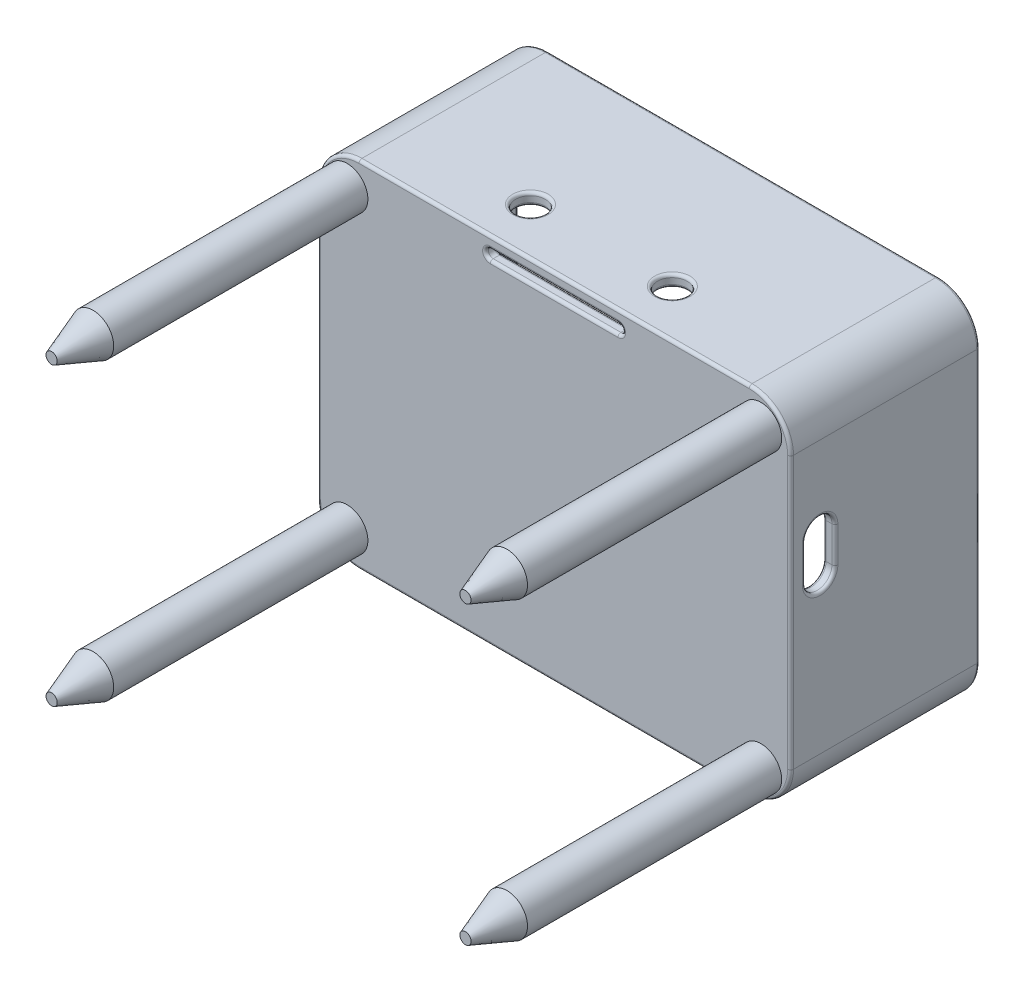
SolidWorks part; units mm, degrees
ref_plane "Plan de face" through (0, 0, 0) normal (0, 0, 1) x (1, 0, 0)
ref_plane "Plan de dessus" through (0, 0, 0) normal (0, 1, 0) x (1, 0, 0)
ref_plane "Plan de droite" through (0, 0, 0) normal (1, 0, 0) x (0, 0, -1)
sketch "Esquisse2" plane through (0, 0, 0) normal (0, 0, 1) x (1, 0, 0)
  line L5 (-33, -30) -> (33, -30)
  line L6 (-40, -23) -> (-40, 23)
  line L7 (-33, 30) -> (33, 30)
  line L8 (40, -23) -> (40, 23)
  line L9 (-40, -30) -> (40, 30) construction
  line L10 (-40, 30) -> (40, -30) construction
  arc A0 (33, 30) -> (40, 23) centre (33, 23) cw
  arc A1 (40, -23) -> (33, -30) centre (33, -23) cw
  arc A2 (-40, -23) -> (-33, -30) centre (-33, -23) ccw
  arc A3 (-40, 23) -> (-33, 30) centre (-33, 23) cw
  point P0 (0, 0)
  dimension "D3" = 7
  dimension "D1" = 60
  dimension "D2" = 80
extrude "Boss.-Extru.1" add sketch "Esquisse2" along normal blind 2
sketch "Esquisse3" plane through (0, 0, 2) normal (0, 0, 1) x (1, 0, 0)
  line L0 (33, 30) -> (-33, 30) construction
  line L1 (-40, 23) -> (-40, -23) construction
  line L2 (-33, -30) -> (33, -30) construction
  line L3 (40, -23) -> (40, 23) construction
  circle A0 centre (-35, 25) radius 3.5
  circle A1 centre (35, 25) radius 3.5
  circle A2 centre (35, -25) radius 3.5
  circle A3 centre (-35, -25) radius 3.5
  dimension "D1" = 7
  dimension "D2" = 5
  dimension "D3" = 5
  dimension "D4" = 5
  dimension "D5" = 5
extrude "Boss.-Extru.2" add sketch "Esquisse3" along normal blind 50
chamfer "Chanfrein1" distance 7 angle 20 4 edges at (38.5, 25, 52) (-31.5, 25, 52) (-31.5, -25, 52) (38.5, -25, 52) first distance on face at (38.5, 25, 52) first distance on face at (-31.5, 25, 52) first distance on face at (-31.5, -25, 52) first distance on face at (38.5, -25, 52)
sketch "Esquisse4" plane through (0, 0, 0) normal (0, 0, -1) x (-1, 0, 0)
  line L12 (-33, 30) -> (33, 30) construction
  line L13 (40, 23) -> (40, -23) construction
  line L14 (33, -30) -> (-33, -30) construction
  line L15 (-33, 30) -> (33, 30)
  line L16 (40, 23) -> (40, -23)
  line L17 (33, -30) -> (-33, -30)
  line L18 (-40, -23) -> (-40, 23) construction
  line L19 (-40, -23) -> (-40, 23)
  line L20 (-33, 28) -> (33, 28)
  line L21 (38, 23) -> (38, -23)
  line L22 (33, -28) -> (-33, -28)
  line L23 (-38, -23) -> (-38, 23)
  arc A0 (40, 23) -> (33, 30) centre (33, 23) ccw construction
  arc A1 (33, -30) -> (40, -23) centre (33, -23) ccw construction
  arc A2 (40, 23) -> (33, 30) centre (33, 23) ccw
  arc A3 (33, -30) -> (40, -23) centre (33, -23) ccw
  arc A4 (-33, 30) -> (-40, 23) centre (-33, 23) ccw construction
  arc A5 (-33, 30) -> (-40, 23) centre (-33, 23) ccw
  arc A6 (-40, -23) -> (-33, -30) centre (-33, -23) ccw construction
  arc A7 (-40, -23) -> (-33, -30) centre (-33, -23) ccw
  arc A8 (38, 23) -> (33, 28) centre (33, 23) ccw
  arc A9 (33, -28) -> (38, -23) centre (33, -23) ccw
  arc A10 (-38, -23) -> (-33, -28) centre (-33, -23) ccw
  arc A11 (-33, 28) -> (-38, 23) centre (-33, 23) ccw
  dimension "D1" = 2
extrude "Boss.-Extru.3" add sketch "Esquisse4" along normal blind 30
sketch "Esquisse5" plane through (40, 0, 0) normal (1, 0, 0) x (0, 0, -1)
  line L0 (3, 9.2) -> (3, 3.2) construction
  line L1 (5.5, 9.2) -> (5.5, 3.2)
  line L2 (0.5, 9.2) -> (0.5, 3.2)
  arc A0 (5.5, 9.2) -> (0.5, 9.2) centre (3, 9.2) ccw
  arc A1 (0.5, 3.2) -> (5.5, 3.2) centre (3, 3.2) ccw
  point P2 (3, 6.2)
  point P7 (3, 7.4852)
  point P8 (3, 11.7)
  point P10 (3, 0.7)
  dimension "D1" = 11
  dimension "D2" = 0.5
  dimension "D3" = 5
  dimension "D4" = 6.2
extrude "Enlèv. mat.-Extru.1" cut sketch "Esquisse5" against normal up to surface (2 mm away) contours L2 A1 L1 A0 up to face at (38, 0, -15)
sketch "Esquisse6" plane through (0, 0, 0) normal (0, 0, -1) x (-1, 0, 0)
  line L0 (-10.8, 27.2) -> (10.8, 27.2) construction
  line L1 (-10.8, 28) -> (10.8, 28)
  line L2 (-10.8, 26.4) -> (10.8, 26.4)
  line L5 (33, 28) -> (-33, 28) construction
  arc A0 (-10.8, 28) -> (-10.8, 26.4) centre (-10.8, 27.2) ccw
  arc A1 (10.8, 26.4) -> (10.8, 28) centre (10.8, 27.2) ccw
  point P0 (18.5903, 18.6488)
  point P3 (0, 27.2)
  point P10 (-11.6, 27.2)
  point P11 (11.6, 27.2)
  dimension "D1" = 23.2
  dimension "D2" = 1.6
extrude "Enlèv. mat.-Extru.2" cut sketch "Esquisse6" against normal up to surface (2 mm away) up to face at (-38.5, -25, 2)
sketch "Esquisse9" plane through (-12, 28, 0) normal (0, -1, 0) x (1, 0, 0)
  line L9 (2.5, -6) -> (21.5, -6) construction
  circle A0 centre (0, -6) radius 2.5
  circle A1 centre (24, -6) radius 2.5
  point P6 (0, 0)
  point P7 (0, 0)
  point P8 (12, -6)
  point P11 (-10.9255, -6)
  dimension "D1" = 5
  dimension "D2" = 6
  dimension "D3" = 19
extrude "Enlèv. mat.-Extru.4" cut sketch "Esquisse9" against normal up to next
sketch "Esquisse10" plane through (-38, 0, 0) normal (1, 0, 0) x (0, 0, -1)
  line L1 (20, 7.5) -> (25, 7.5)
  line L2 (20, 7.5) -> (20, -7.5)
  line L3 (20, -7.5) -> (25, -7.5)
  line L4 (25, 7.5) -> (25, -7.5)
  line L5 (14, -5) -> (14, 5) construction
  circle A0 centre (14, 5) radius 1.5
  circle A1 centre (14, -5) radius 1.5
  point P4 (20, 0)
  point P12 (14, 0)
  point P13 (14, 3.5)
  point P14 (14, -3.5)
  dimension "D4" = 3
  dimension "D1" = 5
  dimension "D2" = 15
  dimension "D3" = 14
  dimension "D5" = 7
  dimension "D6" = 6
extrude "Enlèv. mat.-Extru.5" cut sketch "Esquisse10" against normal through all
sketch "Esquisse11" plane through (0, 0, 0) normal (0, 0, -1) x (-1, 0, 0)
  line L0 (-38, 23) -> (-38, -23) construction
  line L1 (-38, 17.1) -> (-33.5, 17.1)
  line L2 (-38, 17.1) -> (-38, 15.1)
  line L3 (-38, 15.1) -> (-33.5, 15.1)
  line L4 (-33, 16.6) -> (-33, 15.6)
  line L6 (-38, -15.9) -> (-33.5, -15.9)
  line L7 (-38, -15.9) -> (-38, -13.9)
  line L8 (-38, -13.9) -> (-33.5, -13.9)
  line L9 (-33, -15.4) -> (-33, -14.4)
  line L10 (-12.5, -13.9) -> (-8.5, -13.9)
  line L11 (-13, -14.4) -> (-13, -15.4)
  line L12 (-12.5, -15.9) -> (-8.5, -15.9)
  line L13 (-8, -14.4) -> (-8, -15.4)
  line L14 (-12.5, 17.1) -> (-8.5, 17.1)
  line L15 (-13, 16.6) -> (-13, 15.6)
  line L16 (-12.5, 15.1) -> (-8.5, 15.1)
  line L17 (-8, 16.6) -> (-8, 15.6)
  line L18 (25.5, 5) -> (26.5, 5)
  line L19 (25, 4.5) -> (25, -4.5)
  line L20 (25.5, -5) -> (26.5, -5)
  line L21 (27, 4.5) -> (27, -4.5)
  arc A0 (-8, -14.4) -> (-8.5, -13.9) centre (-8.5, -14.4) ccw
  arc A1 (-12.5, -13.9) -> (-13, -14.4) centre (-12.5, -14.4) ccw
  arc A2 (-33.5, -15.9) -> (-33, -15.4) centre (-33.5, -15.4) ccw
  arc A3 (-33, -14.4) -> (-33.5, -13.9) centre (-33.5, -14.4) ccw
  arc A4 (-33.5, 15.1) -> (-33, 15.6) centre (-33.5, 15.6) ccw
  arc A5 (-33, 16.6) -> (-33.5, 17.1) centre (-33.5, 16.6) ccw
  arc A6 (-8, 16.6) -> (-8.5, 17.1) centre (-8.5, 16.6) ccw
  arc A7 (-8, 15.6) -> (-8.5, 15.1) centre (-8.5, 15.6) cw
  arc A8 (-12.5, 15.1) -> (-13, 15.6) centre (-12.5, 15.6) cw
  arc A9 (-13, 16.6) -> (-12.5, 17.1) centre (-12.5, 16.6) cw
  arc A10 (-8, -15.4) -> (-8.5, -15.9) centre (-8.5, -15.4) cw
  arc A11 (-13, -15.4) -> (-12.5, -15.9) centre (-12.5, -15.4) ccw
  arc A12 (26.5, 5) -> (27, 4.5) centre (26.5, 4.5) cw
  arc A13 (25.5, -5) -> (25, -4.5) centre (25.5, -4.5) cw
  arc A14 (26.5, -5) -> (27, -4.5) centre (26.5, -4.5) ccw
  arc A15 (25, 4.5) -> (25.5, 5) centre (25.5, 4.5) cw
  point P22 (25, 0)
  point P25 (0, 0)
  point P26 (0, 0)
  point P27 (-33, 16.1)
  point P38 (-33, 15.1)
  point P41 (-33, 17.1)
  point P44 (-8, 17.1)
  point P51 (-13, 17.1)
  point P60 (25, -5)
  point P65 (25, 5)
  dimension "D9" = 0.5
  dimension "D10" = 0.5
  dimension "D11" = 0.5
  dimension "D12" = 0.5
  dimension "D13" = 0.5
  dimension "D1" = 2
  dimension "D2" = 3.4
  dimension "D3" = 5
  dimension "D4" = 5
  dimension "D5" = 29
  dimension "D6" = 20
  dimension "D7" = 63
  dimension "D8" = 10
extrude "Boss.-Extru.5" add sketch "Esquisse11" along normal blind 9
fillet "Congé1" radius 0.5 109 edges at (-39, -7.5, -25) (-39, -7.5, -20) (-39, 7.5, -20) (-39, 7.5, -25) (38, -15.9, -4.5) (38, -14.9, -9) (-38, 7.5, -22.5) (-38, -7.5, -22.5) (35.75, -15.9, -9) (33.1464, -15.7536, -9) (33, -14.9, -9) (33.1464, -14.0464, -9) (35.75, -15.9, 0) (33.1464, -15.7536, 0) (33, -14.9, 0) (33.1464, -14.0464, 0) (8.1464, 16.9536, -9) (8, 16.1, -9) (8.1464, 15.2464, -9) (10.5, 15.1, -9) (12.8536, 15.2464, -9) (13, 16.1, -9) (12.8536, 16.9536, -9) (8.1464, 16.9536, 0) (8, 16.1, 0) (8.1464, 15.2464, 0) (10.5, 15.1, 0) (12.8536, 15.2464, 0) (13, 16.1, 0) (12.8536, 16.9536, 0) (0, 26.4, 2) (-11.6, 27.2, 2) (0, 28, 2) (11.6, 27.2, 0) (-11.6, 27.2, 0) (40, 11.7, -3) (40, 6.2, -5.5) (40, 0.7, -3) (38, 11.7, -3) (38, 6.2, -5.5) (38, 0.7, -3) (35.75, 15.1, -9) (33.1464, 15.2464, -9) (33, 16.1, -9) (33.1464, 16.9536, -9) (8.1464, -14.0464, -9) (8, -14.9, -9) (8.1464, -15.7536, -9) (10.5, -15.9, -9) (12.8536, -15.7536, -9) (13, -14.9, -9) (12.8536, -14.0464, -9) (-25.1464, 4.8536, -9) (-26, 5, -9) (-26.8536, 4.8536, -9) (-27, 0, -9) (-26.8536, -4.8536, -9) (-26, -5, -9) (-25.1464, -4.8536, -9) (35.75, -13.9, -9) (38, -13.9, -4.5) (35.75, -13.9, 0) (10.5, 17.1, -9) (10.5, 17.1, 0) (-40, -7.5, -22.5) (-40, 7.5, -22.5) (-38, 0, -25) (-40, 0, -25) (-38, 0, -20) (-40, 0, -20) (11.6, 27.2, 2) (0, 26.4, 0) (40, 6.2, -0.5) (38, 6.2, -0.5) (35.75, 17.1, -9) (10.5, -13.9, -9) (-25, 0, -9) (-40, 5, -15.5) (-40, -5, -15.5) (-38, -5, -15.5) (-38, 5, -15.5) (36.5355, -26.5355, -30) (38, 0, -30) (36.5355, 26.5355, -30) (0, 28, -30) (-36.5355, 26.5355, -30) (-38, 0, -30) (-36.5355, -26.5355, -30) (-37.9497, -27.9497, -30) (0, -30, -30) (37.9497, -27.9497, -30) (40, 0, -30) (37.9497, 27.9497, -30) (0, 30, -30) (-37.9497, 27.9497, -30) (-37.9497, 27.9497, 2) (0, 30, 2) (37.9497, 27.9497, 2) (40, 0, 2) (37.9497, -27.9497, 2) (0, -30, 2) (-37.9497, -27.9497, 2) (0, -28, -30) (-40, 0, -30) (-40, 0, 2) (12, 30, -8.5) (12, 28, -8.5) (-12, 30, -8.5) (-12, 28, -8.5)
sketch "Esquisse12" plane through (0, 28, 0) normal (0, -1, 0) x (1, 0, 0)
  line L0 (-12, -6) -> (12, -6) construction
  line L1 (-10.8, 0) -> (10.8, 0) construction
  circle A0 centre (-12, -6) radius 2.5
  circle A1 centre (12, -6) radius 2.5
  point P4 (0, -6)
  point P8 (-9.5, -6)
  point P9 (9.5, -6)
  dimension "D3" = 5
  dimension "D1" = 6
  dimension "D2" = 19
sketch "Esquisse13" plane through (0, -28, 0) normal (0, 1, 0) x (1, 0, 0)
  line L0 (33, 0) -> (-33, 0) construction
  line L1 (-4.5, 10) -> (4.5, 10)
  line L2 (-5, 10.5) -> (-5, 25)
  line L3 (-4.5, 25.5) -> (4.5, 25.5)
  line L4 (5, 10.5) -> (5, 25)
  line L5 (-33, 0) -> (33, 0) construction
  arc A0 (-4.5, 10) -> (-5, 10.5) centre (-4.5, 10.5) cw
  arc A1 (5, 10.5) -> (4.5, 10) centre (4.5, 10.5) cw
  arc A2 (5, 25) -> (4.5, 25.5) centre (4.5, 25) ccw
  arc A3 (-5, 25) -> (-4.5, 25.5) centre (-4.5, 25) cw
  point P10 (0, 10)
  point P11 (0, 0)
  point P16 (5, 10)
  point P19 (5, 25.5)
  point P22 (-5, 25.5)
  dimension "D4" = 0.5
  dimension "D1" = 15.5
  dimension "D2" = 10
  dimension "D3" = 10
extrude "Enlèv. mat.-Extru.7" cut sketch "Esquisse13" against normal blind 0.5
sketch "Esquisse14" plane through (0, -30, 0) normal (0, -1, 0) x (1, 0, 0)
  line L1 (4.5, -25.5) -> (-4.5, -25.5) construction
  circle A0 centre (0, -20.5) radius 4
  point P2 (3.5303, -16.9522)
  dimension "D1" = 8
  dimension "D2" = 5
extrude "Enlèv. mat.-Extru.8" cut sketch "Esquisse14" against normal blind 0.5
fillet "Congé2" radius 0.5 1 edges at (0, -30, -24.5)
fillet "Congé3" radius 0.5 1 edges at (0, -29.5, -24.5)
